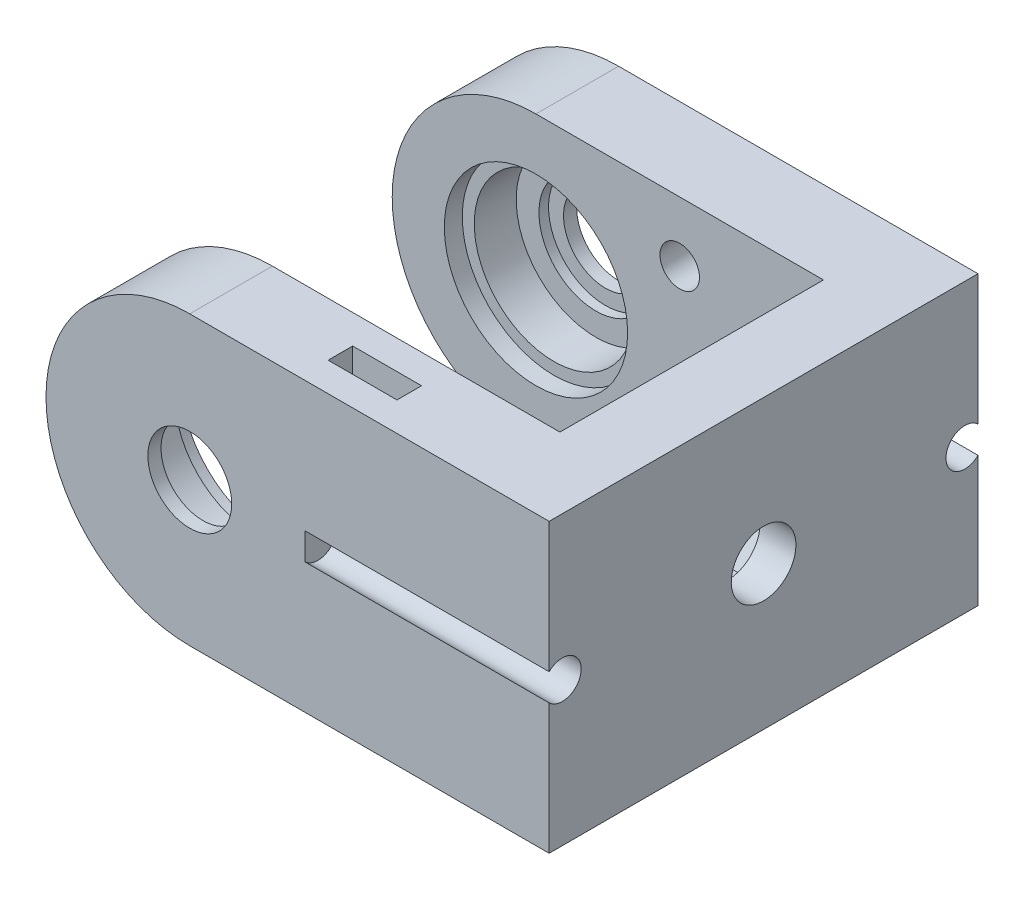
SolidWorks part; units mm, degrees
ref_plane "Front Plane" through (0, 0, 0) normal (0, 0, 1) x (1, 0, 0)
ref_plane "Top Plane" through (0, 0, 0) normal (0, 1, 0) x (1, 0, 0)
ref_plane "Right Plane" through (0, 0, 0) normal (1, 0, 0) x (0, 0, -1)
sketch "Sketch2" plane through (0, 0, 0) normal (0, 0, 1) x (1, 0, 0)
  line L0 (-53.0246, 0) -> (65.6054, 0) construction
  line L1 (-30, -12) -> (0, -12)
  line L2 (0, -12) -> (0, 12)
  line L3 (0, 12) -> (-30, 12)
  circle A0 centre (-30, 0) radius 12 construction
  arc A1 (-30, 12) -> (-30, -12) centre (-30, 0) ccw
  point P7 (-42, 0)
  dimension "D1" = 24
  dimension "D2" = 42
extrude "Boss-Extrude1" add sketch "Sketch2" along normal blind 17.9 and the other way blind 17.9
sketch "Sketch3" plane through (0, 0, 0) normal (0, 1, 0) x (1, 0, 0)
  line L0 (-42, 0) -> (0, 0) construction
  line L1 (-42, 17.9) -> (-42, -17.9) construction
  line L2 (0, -17.9) -> (0, 17.9) construction
  line L3 (-42, -11) -> (-42, 11)
  line L4 (-42, 11) -> (-6, 11)
  line L5 (-6, 11) -> (-6, -11)
  line L7 (-42, -11) -> (-6, -11)
  line L8 (-30, 17.9) -> (-42, 17.9) construction
  point P12 (-6, 0)
  dimension "D2" = 6
  dimension "D1" = 6.9
extrude "Cut-Extrude1" cut sketch "Sketch3" along normal through all both and the other way through all
sketch "Sketch4" plane through (0, 0, 0) normal (0, 0, 1) x (1, 0, 0)
  circle A0 centre (-30, 0) radius 7.65
  dimension "D1" = 15.3
extrude "Cut-Extrude2" cut sketch "Sketch4" against normal blind 12.5 and the other way blind 12.5
sketch "Sketch5" plane through (0, 0, 0) normal (0, 0, 1) x (1, 0, 0)
  circle A0 centre (-30, 0) radius 6.65
  dimension "D1" = 13.3
extrude "Cut-Extrude3" cut sketch "Sketch5" against normal blind 16 and the other way blind 16
sketch "Sketch6" plane through (0, 0, 0) normal (0, 0, 1) x (1, 0, 0)
  circle A0 centre (-30, 0) radius 4.75
  dimension "D1" = 9.5
extrude "Cut-Extrude4" cut sketch "Sketch6" against normal blind 16.8 and the other way blind 16.8
sketch "Sketch7" plane through (0, 0, 0) normal (0, 0, 1) x (1, 0, 0)
  circle A0 centre (-30, 0) radius 3.5
  dimension "D1" = 7
extrude "Cut-Extrude5" cut sketch "Sketch7" against normal through all both and the other way through all
sketch "Sketch10" plane through (0, 0, 0) normal (1, 0, 0) x (0, 0, -1)
  line L0 (-17.9, 0) -> (17.9, 0) construction
  line L1 (-17.9, -12) -> (-17.9, 12) construction
  line L2 (-17.9, 1.1272) -> (-17.9, -1.1272)
  line L3 (0, 0) -> (0, 12) construction
  line L4 (17.9, 12) -> (-17.9, 12) construction
  line L11 (-18.4833, 11.2545) -> (-18.4833, -12.7455) construction
  line L12 (17.9, 1.1272) -> (17.9, -1.1272)
  circle A12 centre (-16.8, 0) radius 1.575 construction
  circle A13 centre (-19.5833, 1.475) radius 1.575 construction
  circle A14 centre (-19.5833, -1.475) radius 1.575 construction
  arc A15 (-17.9, 1.1272) -> (-17.9, -1.1272) centre (-16.8, 0) cw
  arc A16 (17.9, 1.1272) -> (17.9, -1.1272) centre (16.8, 0) ccw
  point P12 (-18.375, 0)
  dimension "D1" = 3.15
  dimension "D3" = 3.15
  dimension "D6" = 0.5833
  dimension "D2" = 1.1
  dimension "D4" = 1.1
  dimension "D5" = 2.95
extrude "Cut-Extrude6" cut sketch "Sketch10" against normal blind 20.4 and the other way through all
sketch "Sketch11" plane through (0, 0, 0) normal (1, 0, 0) x (0, 0, -1)
  circle A0 centre (0, 0) radius 2.7
  dimension "D1" = 5.4
extrude "Cut-Extrude7" cut sketch "Sketch11" against normal through all both and the other way through all
sketch "Sketch12" plane through (-6, 0, 0) normal (-1, 0, 0) x (0, 0, 1)
  line L1 (-4.7054, 0) -> (-2.3527, -4.075)
  line L2 (-2.3527, -4.075) -> (2.3527, -4.075)
  line L3 (2.3527, -4.075) -> (4.7054, 0)
  line L4 (4.7054, 0) -> (2.3527, 4.075)
  line L5 (2.3527, 4.075) -> (-2.3527, 4.075)
  line L6 (-2.3527, 4.075) -> (-4.7054, 0)
  circle A1 centre (0, 0) radius 4.075 construction
  dimension "D1" = 8.15
extrude "Cut-Extrude8" cut sketch "Sketch12" against normal blind 3
sketch "Sketch14" plane through (0, 0, -17.9) normal (0, 0, -1) x (-1, 0, 0)
  line L0 (30, -12) -> (0, -12) construction
  circle A0 centre (18, -7) radius 1.65
  circle A1 centre (30, 0) radius 8 construction
  point P8 (18, 1.1272)
  point P12 (18, -2.9624)
  dimension "D2" = 16
  dimension "D3" = 3.3
  dimension "D1" = 12
  dimension "D4" = 5
extrude "Cut-Extrude10" cut sketch "Sketch14" against normal blind 33.3
sketch "Sketch15" plane through (0, 0, -17.9) normal (0, 0, -1) x (-1, 0, 0)
  circle A0 centre (18, -7) radius 2.7
  dimension "D1" = 5.4
extrude "Cut-Extrude11" cut sketch "Sketch15" against normal blind 3.3
sketch "Sketch16" plane through (0, -12, 0) normal (0, -1, 0) x (1, 0, 0)
  line L0 (-30, 11) -> (-6, 11) construction
  line L1 (-20.875, 13.425) -> (-15.125, 13.425)
  line L2 (-20.875, 13.425) -> (-20.875, 15.475)
  line L3 (-20.875, 15.475) -> (-15.125, 15.475)
  line L4 (-15.125, 13.425) -> (-15.125, 15.475)
  line L5 (-20.875, 13.425) -> (-15.125, 15.475) construction
  line L6 (-20.875, 15.475) -> (-15.125, 13.425) construction
  line L7 (-30, 17.9) -> (0, 17.9) construction
  line L8 (-18, 17.9) -> (-18, 11) construction
  line L10 (-19.65, 11) -> (-16.35, 11) construction
  point P0 (-18, 14.45)
  point P6 (-18, 14.45)
  dimension "D2" = 5.75
  dimension "D3" = 2.05
extrude "Cut-Extrude12" cut sketch "Sketch16" against normal blind 7.665
mirror "Mirror1" about plane through (0, 0, 0) normal (0, 1, 0) of "Cut-Extrude10", "Cut-Extrude11", "Cut-Extrude12"
equation "\"w\"= 6.9mm'Width of section holding bearings"
equation "\"d\"= 22mm'Distance between walls"
equation "\"D1@Boss-Extrude1\"=\"hd\"+\"w\""
equation "\"D2@Boss-Extrude1\"=\"hd\"+\"w\""
equation "\"øob\"= 15.3mm'Bearing out diameter"
equation "\"øib\"= 13.3mm'Bearing inner diameter"
equation "\"fwb\"= 1.5mm'Bearing flange width"
equation "\"wb\"= 3.5mm'Bearing width"
equation "\"hd\"= \"d\" / 2'Half distance"
equation "\"D1@Sketch3\"=\"w\""
equation "\"ws\"= 6mm'Second width"
equation "\"D2@Sketch3\"=\"ws\""
equation "\"mh\"= 24mm'Main height of the part"
equation "\"mw\"= 42mm'Main width of the part"
equation "\"D1@Sketch2\"=\"mh\""
equation "\"D2@Sketch2\"=\"mw\""
equation "\"D1@Sketch4\"=\"øob\""
equation "\"D1@Cut-Extrude2\"=\"hd\"+ \"fwb\""
equation "\"D2@Cut-Extrude2\"=\"hd\"+ \"fwb\""
equation "\"D1@Sketch5\"=\"øib\""
equation "\"D1@Cut-Extrude3\"=\"hd\"+ \"fwb\" + \"wb\""
equation "\"D2@Cut-Extrude3\"=\"hd\"+ \"fwb\" +\"wb\""
equation "\"D1@Cut-Extrude4\"=\"hd\"+\"fwb\"+ \"wb\"+0.8mm"
equation "\"D2@Cut-Extrude4\"=\"hd\"+\"fwb\"+ \"wb\"+0.8mm"
